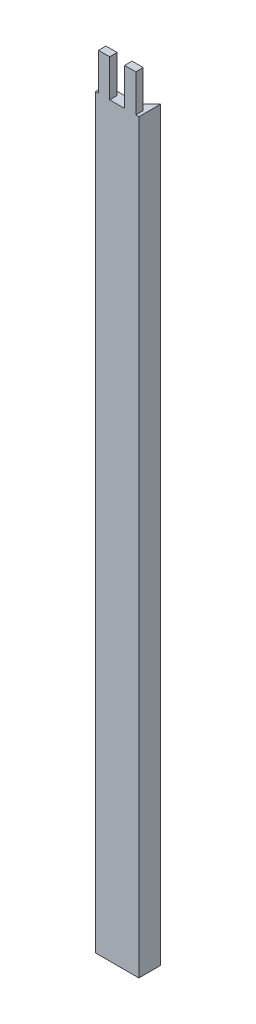
SolidWorks part; units mm, degrees
ref_plane "Front Plane" through (0, 0, 0) normal (0, 0, 1) x (1, 0, 0)
ref_plane "Top Plane" through (0, 0, 0) normal (0, 1, 0) x (1, 0, 0)
ref_plane "Right Plane" through (0, 0, 0) normal (1, 0, 0) x (0, 0, -1)
sketch "Sketch2" plane through (0, 0, 0) normal (0, 0, 1) x (1, 0, 0)
  line L1 (0, 0) -> (-6, 0)
  line L2 (0, 0) -> (0, -200)
  line L3 (0, -200) -> (-6, -200)
  line L4 (-6, 0) -> (-6, -200)
  dimension "D1" = 6
  dimension "D2" = 200
extrude "Boss-Extrude1" add sketch "Sketch2" along normal blind 3
sketch "Sketch4" plane through (0, -200, 0) normal (0, -1, 0) x (-1, 0, 0)
  line L0 (0, 0) -> (-2.8284, 2.8284)
  line L1 (-2.8284, 2.8284) -> (-2.8284, -3)
  line L2 (-2.8284, -3) -> (0, -3)
  line L3 (0, -3) -> (0, 0)
  line L4 (3, 0) -> (3, -3.7119) construction
  line L5 (6, 0) -> (0, 0) construction
  line L6 (8.8284, -3) -> (6, -3)
  line L7 (8.8284, 2.8284) -> (8.8284, -3)
  line L8 (6, 0) -> (8.8284, 2.8284)
  line L9 (6, -3) -> (6, 0)
  dimension "D1" = 135
  dimension "D2" = 4
extrude "Boss-Extrude2" add sketch "Sketch4" against normal up to vertex (200 mm away) up to point (0, 0, 0)
sketch "Sketch5" plane through (0, 0, 0) normal (0, 1, 0) x (1, 0, 0)
  line L0 (2.8284, -3) -> (-8.8284, -3) construction
  line L1 (-8, -3) -> (-5, -3)
  line L2 (-8, -3) -> (-8, -1)
  line L3 (-8, -1) -> (-5, -1)
  line L4 (-5, -3) -> (-5, -1)
  line L5 (-3, 0) -> (-3, -4.0355) construction
  line L6 (0, 0) -> (-6, 0) construction
  line L7 (2, -1) -> (-1, -1)
  line L8 (-1, -3) -> (-1, -1)
  line L9 (2, -3) -> (-1, -3)
  line L10 (2, -3) -> (2, -1)
  dimension "D1" = 3
  dimension "D2" = 2
  dimension "D3" = 2
extrude "Boss-Extrude3" add sketch "Sketch5" along normal blind 10
